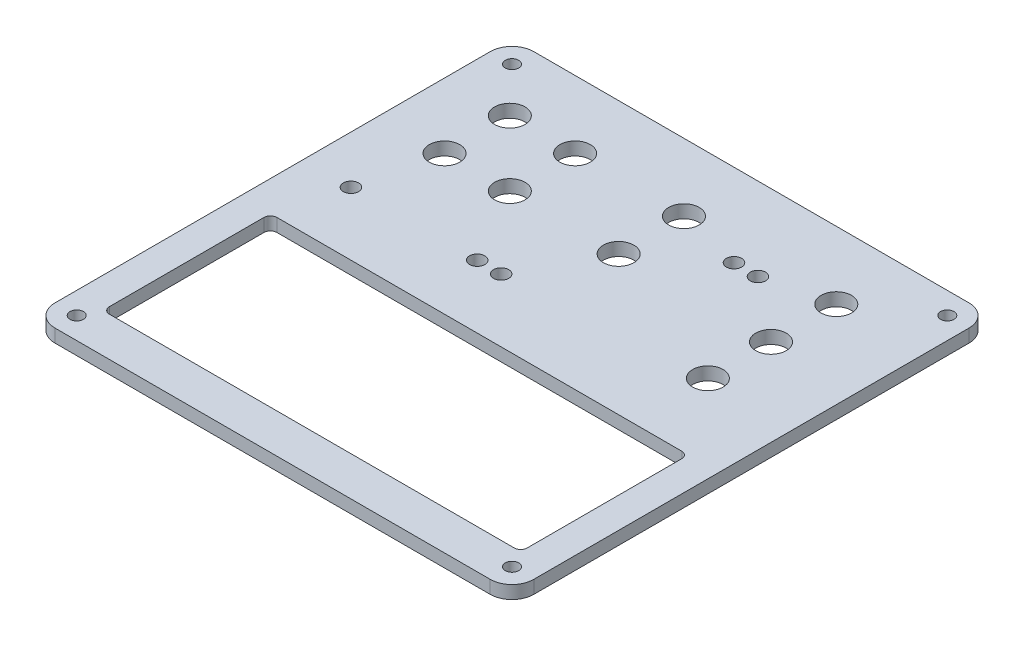
SolidWorks part; units mm, degrees
ref_plane "Front Plane" through (0, 0, 0) normal (0, 0, 1) x (1, 0, 0)
ref_plane "Top Plane" through (0, 0, 0) normal (0, 1, 0) x (1, 0, 0)
ref_plane "Right Plane" through (0, 0, 0) normal (1, 0, 0) x (0, 0, -1)
sketch "Sketch1" plane through (0, 0, 0) normal (0, 1, 0) x (1, 0, 0)
  line L1 (-55, 55) -> (55, 55)
  line L2 (-55, 55) -> (-55, -55)
  line L3 (-55, -55) -> (55, -55)
  line L4 (55, 55) -> (55, -55)
  line L5 (-55, 55) -> (55, -55) construction
  line L6 (-55, -55) -> (55, 55) construction
  circle A0 centre (-50, 50) radius 1.55
  circle A1 centre (50, 50) radius 1.55
  circle A2 centre (50, -50) radius 1.55
  circle A3 centre (-50, -50) radius 1.55
  point P0 (0, 0)
  dimension "D4" = 3.1
  dimension "D8" = 3.1
  dimension "D9" = 3.1
  dimension "D10" = 3.1
  dimension "D1" = 110
  dimension "D2" = 110
  dimension "D3" = 5
  dimension "D5" = 5
  dimension "D6" = 5
  dimension "D7" = 5
extrude "Boss-Extrude1" add sketch "Sketch1" along normal blind 3 contours A3 | A2 | A1 | A0 | L1 L4 L3 L2
fillet "Fillet1" radius 5 4 edges at (-55, 1.5, -55) (55, 1.5, -55) (55, 1.5, 55) (-55, 1.5, 55)
sketch "Sketch2" plane through (0, 3, 0) normal (0, 1, 0) x (1, 0, 0)
  line L0 (0, 55) -> (0, -55) construction
  line L1 (-48, -46) -> (48, -46)
  line L2 (-48, -46) -> (-48, -7.5)
  line L3 (-48, -7.5) -> (48, -7.5)
  line L4 (48, -46) -> (48, -7.5)
  line L5 (-50, 55) -> (50, 55) construction
  line L6 (-50, -55) -> (50, -55) construction
  line L7 (-55, 50) -> (-55, -50) construction
  line L8 (55, 50) -> (55, -50) construction
  dimension "D1" = 7
  dimension "D2" = 7
  dimension "D3" = 38.5
  dimension "D4" = 9
extrude "Cut-Extrude1" cut sketch "Sketch2" against normal through all contours L3 L4 L1 L2
fillet "Fillet2" radius 1.5 4 edges at (-48, 1.5, 46) (48, 1.5, 46) (48, 1.5, 7.5) (-48, 1.5, 7.5)
sketch "Sketch3" plane through (0, 3, 0) normal (0, 1, 0) x (1, 0, 0)
  line L0 (35, 55) -> (35, -55) construction
  line L1 (-55, 50) -> (-55, -50) construction
  line L2 (-55, 39.5) -> (55, 39.5) construction
  line L3 (55, 50) -> (55, -50) construction
  line L4 (-55, 24.5) -> (55, 24.5) construction
  line L5 (-55, 9.5) -> (55, 9.5) construction
  line L6 (-40, 55) -> (-40, -55) construction
  line L7 (-50, 55) -> (50, 55) construction
  line L8 (-50, -55) -> (50, -55) construction
  line L9 (-25, 55) -> (-25, -55) construction
  line L10 (0, 55) -> (0, -55) construction
  circle A0 centre (-40, 39.5) radius 3.5
  circle A1 centre (-40, 24.5) radius 3.5
  circle A3 centre (-25, 39.5) radius 3.5
  circle A4 centre (-25, 24.5) radius 3.5
  circle A5 centre (0, 39.5) radius 3.5
  circle A6 centre (0, 24.5) radius 3.5
  circle A7 centre (35, 39.5) radius 3.5
  circle A8 centre (35, 24.5) radius 3.5
  circle A9 centre (35, 10) radius 3.5
  dimension "D3" = 7
  dimension "D4" = 7
  dimension "D5" = 7
  dimension "D8" = 7
  dimension "D9" = 15
  dimension "D11" = 7
  dimension "D12" = 7
  dimension "D13" = 7
  dimension "D15" = 7
  dimension "D16" = 7
  dimension "D1" = 15
  dimension "D2" = 15.5
  dimension "D6" = 15
  dimension "D7" = 15
  dimension "D10" = 25
  dimension "D14" = 35
extrude "Cut-Extrude2" cut sketch "Sketch3" against normal through all contours A1 | A3 | A4 | A5 | A6 | A0 | A7 | A8 | A9 region at (-40, 3, -24.5) region at (-25, 3, -39.5) region at (-25, 3, -24.5) region at (0, 3, -39.5) region at (0, 3, -24.5)
sketch "Sketch4" plane through (0, 3, 0) normal (0, 1, 0) x (1, 0, 0)
  line L1 (-55, 50) -> (-55, -50) construction
  line L2 (55, 50) -> (55, -50) construction
  line L3 (-44, -55) -> (-44, 55) construction
  line L4 (-50, -55) -> (50, -55) construction
  line L5 (-50, 55) -> (50, 55) construction
  line L6 (-15, 55) -> (-15, -55) construction
  line L7 (-55, 7) -> (55, 7) construction
  line L8 (-55, 36) -> (55, 36) construction
  line L9 (15, 55) -> (15, -55) construction
  circle A0 centre (-44, 7) radius 1.75
  circle A1 centre (-15, 7) radius 1.75
  circle A2 centre (-9.5, 7) radius 1.75
  circle A3 centre (15, 36) radius 1.75
  circle A4 centre (20.5, 36) radius 1.75
  dimension "D3" = 3.5
  dimension "D4" = 40
  dimension "D6" = 3.5
  dimension "D8" = 3.5
  dimension "D9" = 3.5
  dimension "D10" = 3.5
  dimension "D1" = 11
  dimension "D5" = 62
  dimension "D7" = 5.5
  dimension "D11" = 5.5
  dimension "D12" = 40
  dimension "D13" = 19
extrude "Cut-Extrude3" cut sketch "Sketch4" against normal through all contours A0 | A1 | A2 | A3 | A4
